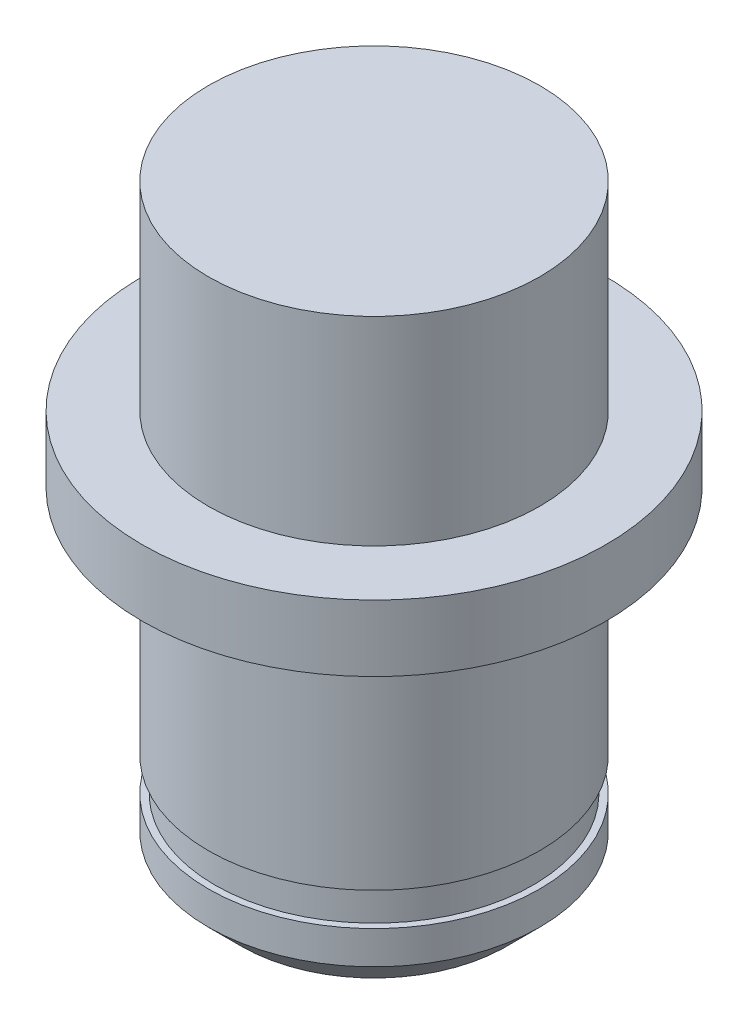
SolidWorks part; units mm, degrees
material "Nylon 101"
ref_plane "Front Plane" through (0, 0, 0) normal (0, 0, 1) x (1, 0, 0)
ref_plane "Top Plane" through (0, 0, 0) normal (0, 1, 0) x (1, 0, 0)
ref_plane "Right Plane" through (0, 0, 0) normal (1, 0, 0) x (0, 0, -1)
sketch "Sketch1" plane through (0, 0, 0) normal (0, 1, 0) x (1, 0, 0)
  circle A0 centre (0, 0) radius 5
  dimension "D1" = 10
extrude "Boss-Extrude1" add sketch "Sketch1" along normal blind 18
ref_axis "Axis1" through (0, 18, 0) along (0, -1, 0)
sketch "Sketch2" plane through (0, 0, 0) normal (1, 0, 0) x (0, 0, -1)
  line L0 (5, 0) -> (5, 18) construction
  line L1 (4.8, 3) -> (5, 3)
  line L2 (4.8, 3) -> (4.8, 2)
  line L3 (4.8, 2) -> (5, 2)
  line L4 (5, 3) -> (5, 2)
  line L5 (5, 18) -> (-5, 18) construction
  line L6 (5, 12) -> (7, 12)
  line L7 (5, 12) -> (5, 10)
  line L8 (5, 10) -> (7, 10)
  line L9 (7, 12) -> (7, 10)
  dimension "D1" = 7
  dimension "D2" = 2
  dimension "D3" = 6
  dimension "D4" = 1
  dimension "D5" = 4.8
  dimension "D6" = 7
revolve "Revolve1" add sketch "Sketch2" angle 360 about axis through (0, 18, 0) along (0, -1, 0) region at (0, 11, -6)
revolve "Cut-Revolve1" cut sketch "Sketch2<5>" angle 360 about axis through (0, 18, 0) along (0, -1, 0) region at (0, 2.5, -4.9)
sketch "Sketch2<5>" plane through (0, 0, 0) normal (1, 0, 0) x (0, 0, -1) same geometry as "Sketch2"
chamfer "Chamfer2" distance 1 angle 45 1 edges at (0, 0, 5)
